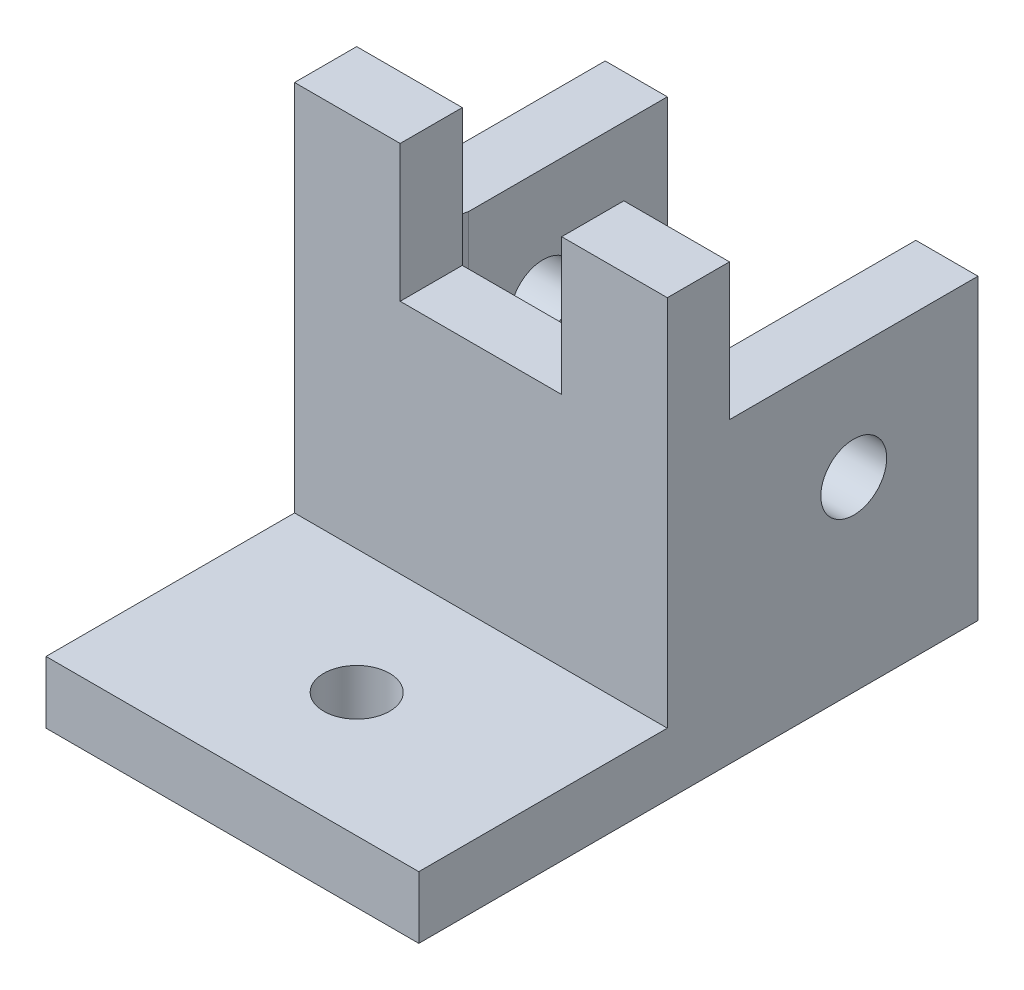
SolidWorks part; units mm, degrees
ref_plane "Front Plane" through (0, 0, 0) normal (0, 0, 1) x (1, 0, 0)
ref_plane "Top Plane" through (0, 0, 0) normal (0, 1, 0) x (1, 0, 0)
ref_plane "Right Plane" through (0, 0, 0) normal (1, 0, 0) x (0, 0, -1)
sketch "Sketch1" plane through (0, 0, 0) normal (0, 1, 0) x (1, 0, 0)
  line L1 (0, 0) -> (30, 0)
  line L2 (0, 0) -> (0, 45)
  line L3 (0, 45) -> (30, 45)
  line L4 (30, 0) -> (30, 45)
  dimension "D1" = 30
  dimension "D2" = 45
extrude "Boss-Extrude1" add sketch "Sketch1" along normal blind 5
sketch "Sketch2" plane through (0, 5, 0) normal (0, 1, 0) x (1, 0, 0)
  line L11 (0, 45) -> (0, 0) construction
  line L12 (0, 25) -> (30, 25)
  line L13 (0, 25) -> (0, 20)
  line L14 (0, 20) -> (30, 20)
  line L15 (30, 25) -> (30, 20)
  line L16 (30, 0) -> (30, 45) construction
  line L17 (30, 45) -> (0, 45) construction
  dimension "D1" = 5
  dimension "D2" = 20
extrude "Boss-Extrude2" add sketch "Sketch2" along normal blind 30
sketch "Sketch3" plane through (0, 5, 0) normal (0, 1, 0) x (1, 0, 0)
  line L1 (0, 25) -> (5, 25)
  line L2 (0, 25) -> (0, 45)
  line L3 (0, 45) -> (5, 45)
  line L4 (5, 25) -> (5, 45)
  line L5 (30, 45) -> (0, 45) construction
  line L6 (0, 45) -> (0, 25) construction
  line L7 (25, 45) -> (30, 45)
  line L8 (25, 45) -> (25, 25)
  line L9 (25, 25) -> (30, 25)
  line L10 (30, 45) -> (30, 25)
  line L11 (0, 25) -> (30, 25) construction
  dimension "D1" = 5
  dimension "D2" = 5
  dimension "D3" = 20
  dimension "D4" = 0
extrude "Boss-Extrude3" add sketch "Sketch3" along normal blind 19
sketch "Sketch4" plane through (0, 35, 0) normal (0, 1, 0) x (1, 0, 0)
  line L0 (0, 20) -> (30, 20) construction
  line L1 (8.5, 20) -> (21.5, 20)
  line L2 (8.5, 20) -> (8.5, 25)
  line L3 (8.5, 25) -> (21.5, 25)
  line L4 (21.5, 20) -> (21.5, 25)
  line L5 (0, 25) -> (30, 25) construction
  line L6 (0, 25) -> (0, 20) construction
  dimension "D1" = 13
  dimension "D2" = 8.5
extrude "Cut-Extrude1" cut sketch "Sketch4" against normal blind 11
sketch "Sketch5" plane through (0, 0, 0) normal (0, -1, 0) x (1, 0, 0)
  line L0 (0, 0) -> (30, 0) construction
  line L1 (30, 0) -> (30, -45) construction
  line L2 (30, -45) -> (0, -45) construction
  circle A0 centre (15, -10) radius 2.65
  circle A1 centre (15, -35) radius 2.65
  dimension "D1" = 5.3
  dimension "D4" = 5.3
  dimension "D2" = 10
  dimension "D3" = 15
  dimension "D5" = 10
  dimension "D6" = 15
extrude "Cut-Extrude2" cut sketch "Sketch5" against normal blind 10
sketch "Sketch6" plane through (30, 0, 0) normal (1, 0, 0) x (0, 0, -1)
  line L0 (45, 24) -> (45, 0) construction
  line L1 (0, 0) -> (45, 0) construction
  circle A0 centre (35, 15) radius 2.65
  dimension "D1" = 5.3
  dimension "D2" = 10
  dimension "D3" = 15
extrude "Cut-Extrude3" cut sketch "Sketch6" against normal through all both and the other way through all
sketch "Sketch7" plane through (0, 0, -45) normal (0, 0, -1) x (-1, 0, 0)
  line L0 (-25, 5) -> (-26, 5)
  line L1 (-26, 5) -> (-25, 9)
  line L2 (-25, 24) -> (-25, 5) construction
  line L3 (-25, 9) -> (-25, 5)
  line L4 (-5, 5) -> (-4, 5)
  line L5 (-4, 5) -> (-5, 9)
  line L6 (-5, 24) -> (-5, 5) construction
  line L7 (-5, 9) -> (-5, 5)
  dimension "D1" = 4
  dimension "D2" = 4
  dimension "D3" = 1
  dimension "D4" = 1
extrude "Cut-Extrude4" cut sketch "Sketch7" against normal up to surface (20 mm away) up to face at (15, 24.5, -25)
sketch "Sketch8" plane through (0, 24, 0) normal (0, 1, 0) x (1, 0, 0)
  line L0 (25, 25) -> (26, 25)
  line L1 (25, 25) -> (30, 25) construction
  line L2 (26, 25) -> (25, 29)
  line L3 (25, 45) -> (25, 25) construction
  line L4 (25, 29) -> (25, 25)
  line L5 (5, 25) -> (5, 29)
  line L6 (5, 25) -> (5, 45) construction
  line L7 (5, 29) -> (4, 25)
  line L8 (8.5, 25) -> (0, 25) construction
  line L9 (4, 25) -> (5, 25)
  dimension "D1" = 1
  dimension "D2" = 4
  dimension "D3" = 1
  dimension "D4" = 4
extrude "Cut-Extrude5" cut sketch "Sketch8" against normal up to surface (19 mm away) up to face at (15, 5, -12.65)
